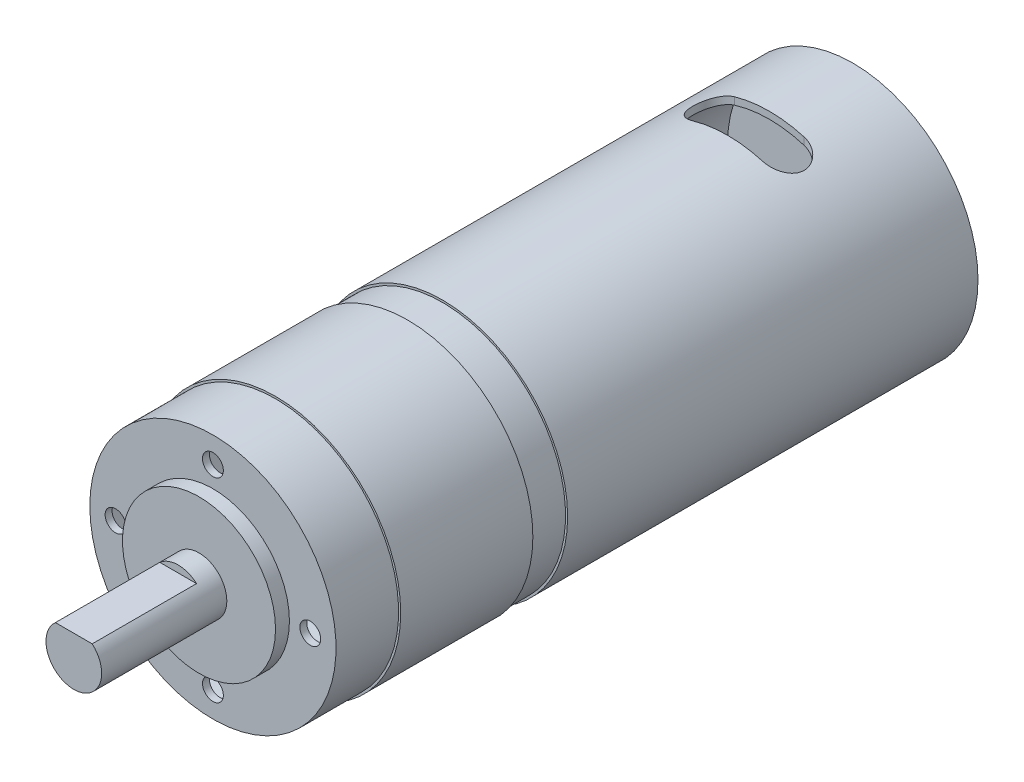
SolidWorks part; units mm, degrees
ref_plane "前视基准面" through (0, 0, 0) normal (0, 0, 1) x (1, 0, 0)
ref_plane "上视基准面" through (0, 0, 0) normal (0, 1, 0) x (1, 0, 0)
ref_plane "右视基准面" through (0, 0, 0) normal (1, 0, 0) x (0, 0, -1)
sketch "草图1" plane through (0, 0, 0) normal (0, 0, 1) x (1, 0, 0)
  circle A0 centre (0, 0) radius 18
  dimension "D1" = 36
extrude "凸台-拉伸1" add sketch "草图1" along normal blind 92
ref_plane "基准面1" through (0, 18, 0) normal (0, 1, 0) x (1, 0, 0)
sketch "草图7" plane through (0, 18, 0) normal (0, 1, 0) x (1, 0, 0)
  line L0 (0, 0) -> (0, -15)
  line L1 (-5, -15) -> (5, -15)
  line L2 (5, -15) -> (-5, -15) construction
  line L3 (5, -18) -> (-5, -18)
  line L4 (5, -12) -> (-5, -12)
  arc A0 (5, -18) -> (5, -12) centre (5, -15) ccw
  arc A1 (-5, -12) -> (-5, -18) centre (-5, -15) ccw
  point P5 (0, -15)
  dimension "D1" = 15
  dimension "D2" = 5
extrude "切除-拉伸2" cut sketch "草图7" against normal blind 36
shell "抽壳8" thickness 1 removed face at (-6.4802, 0, 15) removed face at (6.4802, 0, 15) removed face at (0, 0, 18) removed face at (0, 0, 12)
sketch "草图2" plane through (0, 0, 92) normal (0, 0, 1) x (1, 0, 0)
  circle A0 centre (0, 0) radius 11
  dimension "D1" = 22
extrude "凸台-拉伸2" add sketch "草图2" along normal blind 2
sketch "草图3" plane through (0, 0, 94) normal (0, 0, 1) x (1, 0, 0)
  circle A0 centre (0, 0) radius 4
  dimension "D1" = 8
extrude "凸台-拉伸3" add sketch "草图3" along normal blind 18
sketch "草图4" plane through (0, 0, 112) normal (0, 0, 1) x (1, 0, 0)
  line L0 (0, 4) -> (0, 3)
  line L1 (-2.6458, 3) -> (2.6458, 3)
  circle A0 centre (0, 0) radius 4
  circle M1 centre (0, 0) radius 4
  dimension "D2" = 8
  dimension "D1" = 1
extrude "切除-拉伸1" cut sketch "草图4" against normal blind 15 contours L0 L1 M1 | L1 L0 M1
sketch "草图5" plane through (0, 0, 0) normal (0, 0, -1) x (-1, 0, 0)
  circle A0 centre (0, 0) radius 5
  dimension "D1" = 10
extrude "凸台-拉伸4" add sketch "草图5" along normal blind 3
sketch "草图6" plane through (0, 0, -3) normal (0, 0, -1) x (-1, 0, 0)
  circle A0 centre (0, 0) radius 1.5
  dimension "D1" = 3
extrude "凸台-拉伸5" add sketch "草图6" along normal blind 1
fillet "圆角1" radius 1 2 edges at (-1.5, 0, -4) (-5, 0, -3)
sketch "草图8" plane through (0, 0, 92) normal (0, 0, 1) x (1, 0, 0)
  circle A0 centre (0, 0) radius 14
  circle A1 centre (14, 0) radius 1.5
  circle A2 centre (0, -14) radius 1.5
  circle A3 centre (-14, 0) radius 1.5
  circle A4 centre (0, 14) radius 1.5
  point P14 (0, 0)
  dimension "D1" = 28
  dimension "D2" = 3
  dimension "D3" = 4
extrude "切除-拉伸3" cut sketch "草图8" against normal blind 5 contours A0 A4 | A0 A4 | A0 A1 | A0 A1 | A3 | A2
sketch "草图9" plane through (0, 0, 0) normal (0, 1, 0) x (1, 0, 0)
  line L0 (0, 0) -> (0, -112) construction
  line L1 (-4, -112) -> (4, -112) construction
  line L2 (-18, -92) -> (18, -92) construction
  line L3 (18, -92) -> (17.7, -92)
  line L4 (18, -92) -> (18, -83)
  line L5 (18, -83) -> (17.7, -83)
  line L6 (17.7, -92) -> (17.7, -83)
  line L8 (18, -64) -> (17.7, -64)
  line L9 (18, -64) -> (18, -59)
  line L10 (18, -59) -> (17.7, -59)
  line L11 (17.7, -64) -> (17.7, -59)
  dimension "D1" = 0.3
  dimension "D2" = 0.3
  dimension "D3" = 9
  dimension "D4" = 19
  dimension "D5" = 5
revolve "切除-旋转1" cut sketch "草图9" angle 360 about L0
